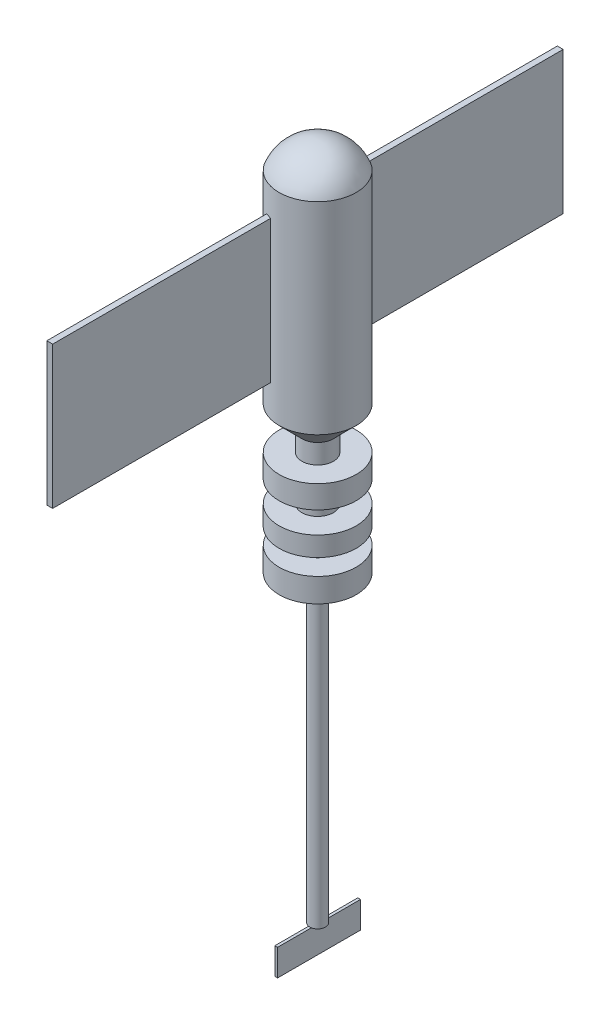
SolidWorks part; units mm, degrees
ref_plane "Front Plane" through (0, 0, 0) normal (0, 0, 1) x (1, 0, 0)
ref_plane "Top Plane" through (0, 0, 0) normal (0, 1, 0) x (1, 0, 0)
ref_plane "Right Plane" through (0, 0, 0) normal (1, 0, 0) x (0, 0, -1)
sketch "Sketch1" plane through (0, 0, 0) normal (0, 0, 1) x (1, 0, 0)
  line L0 (0, 93.0529) -> (0, -62.4434) construction
  line L1 (0, 78.3603) -> (-14.4885, 78.3603)
  line L2 (-14.4885, 78.3603) -> (-14.4885, 2.4488)
  line L3 (-14.4885, 2.4488) -> (-5.9178, -6.1219)
  line L4 (-5.9178, -6.1219) -> (-5.9178, -13.4682)
  line L5 (-5.9178, -13.4682) -> (-14.4885, -13.4682)
  line L6 (-14.4885, -13.4682) -> (-14.4885, -22.0388)
  line L7 (-14.4885, -22.0388) -> (-5.9178, -22.0388)
  line L8 (-5.9178, -22.0388) -> (-5.9178, -30.2014)
  line L9 (-5.9178, -30.2014) -> (-14.4885, -30.2014)
  line L10 (-14.4885, -30.2014) -> (-14.4885, -37.5477)
  line L11 (-14.4885, -37.5477) -> (-5.9178, -37.5477)
  line L12 (-5.9178, -37.5477) -> (-5.9178, -43.6696)
  line L13 (-5.9178, -43.6696) -> (-14.4885, -43.6696)
  line L14 (-14.4885, -43.6696) -> (-14.4885, -52.6484)
  line L15 (-14.4885, -52.6484) -> (-5.9178, -52.6484)
  line L16 (-5.9178, -52.6484) -> (0, -52.6484)
  line L17 (0, -52.6484) -> (0, 78.3603)
revolve "Revolve1" add sketch "Sketch1" angle 360 about L0
dome "Dome1" faces to dome 1 distance 10 reverse direction no elliptical dome no face at (0, 78.3603, 14.4885) parameters "D1"=10
sketch "Sketch4" plane through (0, 0, 0) normal (0, 0, 1) x (1, 0, 0)
  line L1 (-5.8618, 67.909) -> (-3.663, 67.909)
  line L2 (-5.8618, 67.909) -> (-5.8618, 14.395)
  line L3 (-5.8618, 14.395) -> (-3.663, 14.395)
  line L4 (-3.663, 67.909) -> (-3.663, 14.395)
  line L5 (-5.8618, 67.909) -> (-3.663, 14.395) construction
  line L6 (-5.8618, 14.395) -> (-3.663, 67.909) construction
  point P0 (-4.7624, 41.152)
extrude "Boss-Extrude1" add sketch "Sketch4" along normal blind 96
mirror "Mirror1" about plane through (0, 0, 0) normal (0, 0, 1) of "Boss-Extrude1"
sketch "Sketch5" plane through (0, -52.6484, 0) normal (0, -1, 0) x (1, 0, 0)
  circle A0 centre (0, 0) radius 2.9358
extrude "Boss-Extrude2" add sketch "Sketch5" along normal blind 114
sketch "Sketch7" plane through (0, -166.6484, 0) normal (0, -1, 0) x (1, 0, 0)
  line L1 (-0.514, 15.5971) -> (0.514, 15.5971)
  line L2 (-0.514, 15.5971) -> (-0.514, -15.5971)
  line L3 (-0.514, -15.5971) -> (0.514, -15.5971)
  line L4 (0.514, 15.5971) -> (0.514, -15.5971)
  line L5 (-0.514, 15.5971) -> (0.514, -15.5971) construction
  line L6 (-0.514, -15.5971) -> (0.514, 15.5971) construction
  point P0 (0, 0)
extrude "Boss-Extrude3" add sketch "Sketch7" along normal blind 10
